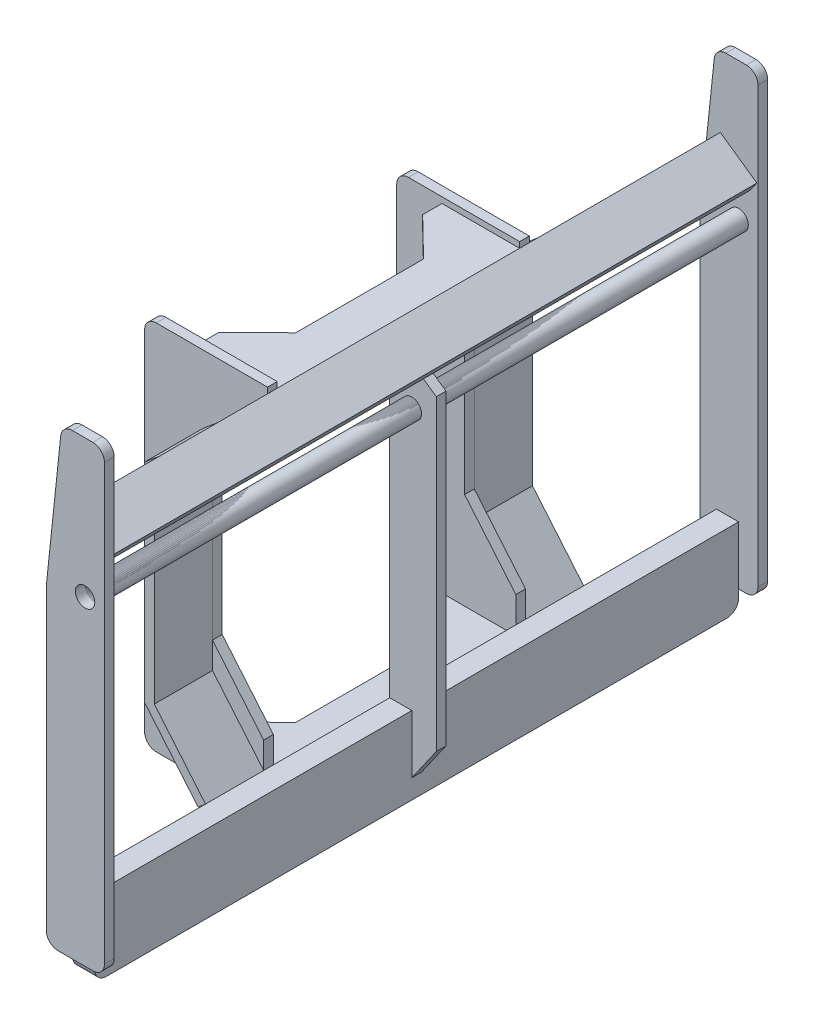
SolidWorks part; units mm, degrees
ref_plane "Front Plane" through (0, 0, 0) normal (0, 0, 1) x (1, 0, 0)
ref_plane "Top Plane" through (0, 0, 0) normal (0, 1, 0) x (1, 0, 0)
ref_plane "Right Plane" through (0, 0, 0) normal (1, 0, 0) x (0, 0, -1)
sketch "Sketch1" plane through (0, 0, 0) normal (0, 0, 1) x (1, 0, 0)
  line L0 (0, 1180) -> (0, 0)
  line L1 (0, 0) -> (-150, 0)
  line L2 (-150, 0) -> (-150, 800)
  line L3 (-150, 800) -> (-110, 1180)
  line L4 (-110, 1180) -> (0, 1180)
  dimension "D1" = 1180
  dimension "D2" = 150
  dimension "D3" = 110
  dimension "D4" = 800
extrude "Boss-Extrude1" add sketch "Sketch1" along normal blind 25 from offset 830
extrude "Boss-Extrude2" add sketch "Sketch1<2>" against normal blind 25 from offset 830 separate body offset against normal yes
sketch "Sketch1<2>" plane through (0, 0, 0) normal (0, 0, 1) x (1, 0, 0) same geometry as "Sketch1"
sketch "Sketch2" plane through (0, 0, -830) normal (0, 0, 1) x (1, 0, 0)
  line L0 (-3, 930) -> (-97.2025, 995.9613)
  line L1 (-3, 930) -> (-20.2073, 905.4254)
  line L2 (-97.2025, 995.9613) -> (-114.4098, 971.3867)
  line L3 (-20.2073, 905.4254) -> (-114.4098, 971.3867)
  line L4 (0, 0) -> (0, 1180) construction
  line L5 (0, 1180) -> (-110, 1180) construction
  line L6 (-150, 0) -> (0, 0) construction
  line L7 (-107, 150) -> (-50, 150)
  line L8 (-107, 150) -> (-107, -50)
  line L9 (-107, -50) -> (-50, -50)
  line L10 (-50, 150) -> (-50, -50)
  line M11 (-150, 0) -> (0, 0)
  dimension "D1" = 30
  dimension "D2" = 115
  dimension "D3" = 3
  dimension "D4" = 250
  dimension "D5" = 55
  dimension "D6" = 57
  dimension "D7" = 50
  dimension "D8" = 150
  dimension "D9" = 200
extrude "Boss-Extrude3" add sketch "Sketch2" along normal up to surface (1660 mm away) contours L3 L1 L0 L2 | L10 L7 L8 M11 | L10 L8 L9 M11 region at (-58.7049, 950.6934, -830) region at (-78.5, 75, -830) region at (-78.5, -25, -830) up to face at (-82, 632, 830)
sketch "Sketch3" plane through (0, 0, 0) normal (0, 0, 1) x (1, 0, 0)
  line L0 (-107, 966.1983) -> (-20.2073, 905.4254)
  line L1 (-20.2073, 905.4254) -> (13, 882.1734)
  line L2 (13, 882.1734) -> (13, 89.9733)
  line L3 (13, 89.9733) -> (-50, 0)
  line L4 (-50, 150) -> (-50, 0) construction
  line L5 (-50, 0) -> (-50, 150)
  line L6 (-50, 150) -> (-107, 150)
  line L7 (-107, 150) -> (-107, 966.1983)
  line L8 (-20.2073, 905.4254) -> (-114.4098, 971.3867) construction
  line L9 (-50, 0) -> (0, 0) construction
  dimension "D1" = 120
  dimension "D2" = 150
  dimension "D3" = 55
extrude "Boss-Extrude4" add sketch "Sketch3" along normal mid plane 25 contours L7 L6 L5 L3 L2 L1 L0 region at (-46.4176, 508.0101, 0)
sketch "Sketch4" plane through (0, 0, 855) normal (0, 0, 1) x (1, 0, 0)
  line L0 (0, 0) -> (0, 1180) construction
  line L1 (0, 1180) -> (-110, 1180) construction
  circle A0 centre (-50, 825) radius 25
  dimension "D1" = 50
  dimension "D2" = 50
  dimension "D3" = 355
extrude "Cut-Extrude1" cut sketch "Sketch4" against normal through all
sketch "Sketch5" plane through (0, 0, 855) normal (0, 0, 1) x (1, 0, 0)
  circle A0 centre (-50, 825) radius 25 construction
  circle A1 centre (-50, 825) radius 25
  circle A2 centre (-50, 825) radius 24.99
  dimension "D1" = 0.01
extrude "Boss-Extrude5" add sketch "Sketch5" against normal up to surface (1710 mm away) up to face at (-25, 825, -855)
sketch "Sketch6" plane through (0, 0, -12.5) normal (0, 0, -1) x (-1, 0, 0)
  line L0 (50, 150) -> (107, 150) construction
  line L1 (114.4098, 971.3867) -> (20.2073, 905.4254) construction
  line L3 (50, 150) -> (107, 150)
  line L4 (114.4098, 971.3867) -> (67.3085, 938.4061)
  line L7 (97.2025, 995.9613) -> (97.2025, 1010.9613)
  line L8 (114.4098, 971.3867) -> (67.3085, 938.4061)
  line L9 (50, 150) -> (107, 150)
  line L10 (97.2025, 1010.9613) -> (414, 1010.9613)
  line L11 (414, 1010.9613) -> (414, 52.9613)
  line L12 (414, 52.9613) -> (107, 52.9613)
  line L13 (107, 0) -> (107, 150) construction
  line L14 (50, 150) -> (239, 375.2414)
  line L15 (239, 375.2414) -> (239, 783.8144)
  line L16 (239, 783.8144) -> (67.3085, 938.4061)
  line L17 (150, 800) -> (150, 0) construction
  line L18 (107, 150) -> (107, 52.9613)
  line L19 (97.2025, 995.9613) -> (114.4098, 971.3867)
  line M2 (107, 150) -> (107, 966.1983)
  dimension "D1" = 77
  dimension "D2" = 175
  dimension "D3" = 89
  dimension "D4" = 50
  dimension "D5" = 15
  dimension "D6" = 958
  dimension "D7" = 57.5
extrude "Boss-Extrude6" add sketch "Sketch6" along normal blind 25 from offset 300 contours L7 L19 L4 L16 L15 L14 L18 L12 L11 L10 M2 region at (-290.6194, 520.2319, -12.5)
sketch "Sketch7" plane through (0, 0, -337.5) normal (0, 0, -1) x (-1, 0, 0)
  line L0 (107, 150) -> (239, 307.3115)
  line L1 (239, 307.3115) -> (239, 823.6719)
  line L2 (239, 823.6719) -> (107, 934.433)
  line L4 (239, 375.2414) -> (239, 783.8144) construction
  line L11 (107, 902.6677) -> (107, 966.1983) construction
  point P6 (0, 0)
  point P7 (107, 934.433)
  point P9 (239, 843.2411)
  point P11 (0, 0)
  dimension "D1" = 130
  dimension "D2" = 140
extrude "Extrude-Thin2" add sketch "Sketch7" along normal blind 150 separate body thin thin type one direction wall 25
sketch "Sketch8" plane through (397.3283, 333.398, 0) normal (0.766, 0.6428, 0) x (0, 0, -1)
  line L4 (337.5, 809.5955) -> (337.5, 784.5955)
  line L5 (337.5, 784.5955) -> (487.5, 784.5955)
  line L6 (487.5, 784.5955) -> (487.5, 809.5955)
  line L7 (487.5, 809.5955) -> (337.5, 809.5955)
  line L8 (337.5, 809.5955) -> (337.5, 784.5955)
  line L9 (337.5, 784.5955) -> (487.5, 784.5955)
  line L10 (487.5, 784.5955) -> (487.5, 809.5955)
  line L11 (487.5, 809.5955) -> (337.5, 809.5955)
  dimension "D1" = 0
extrude "Boss-Extrude8" add sketch "Sketch8" along normal up to next separate body
mirror "Mirror2" about plane through (0, 0, 0) normal (0, 0, 1) of bodies 108 107
ref_plane "Plane1" through (0, 995.9613, 0) normal (0, 1, 0) x (1, 0, 0)
sketch "Sketch9" plane through (0, 995.9613, 0) normal (0, 1, 0) x (1, 0, 0)
  line L0 (-297.2025, 312.5) -> (-97.2025, 312.5)
  line L1 (-97.2025, 312.5) -> (-414, 312.5) construction
  line L2 (-97.2025, -830) -> (-97.2025, 312.5) construction
  line L3 (-97.2025, 312.5) -> (-97.2025, -312.5)
  line L4 (-97.2025, -312.5) -> (-297.2025, -312.5)
  line L5 (-97.2025, -312.5) -> (-414, -312.5) construction
  line L6 (-297.2025, -312.5) -> (-297.2025, -262.5)
  line L7 (-297.2025, -262.5) -> (-197.2025, -164.8664)
  line L8 (-197.2025, -164.8664) -> (-197.2025, 164.8664)
  line L9 (-197.2025, 164.8664) -> (-297.2025, 262.5)
  line L10 (-297.2025, 262.5) -> (-297.2025, 312.5)
  point P6 (-197.2025, 164.8664)
  point P16 (0, 0)
  point P17 (0, 0)
  dimension "D1" = 100
  dimension "D2" = 50
  dimension "D3" = 200
extrude "Boss-Extrude9" add sketch "Sketch9" against normal blind 25
pattern_linear "LPattern1" count 2 spacing 870 along (0, -1, 0) of "Boss-Extrude9"
fillet "Fillet1" radius 30 14 edges at (0, 1180, -842.5) (-110, 1180, -842.5) (0, 1180, 842.5) (-110, 1180, 842.5) (-414, 1010.9613, 325) (-414, 1010.9613, -325) (-150, 0, -842.5) (0, 0, -842.5) (0, 0, 842.5) (-150, 0, 842.5) (-78.5, -50, -830) (-78.5, -50, 830) (-414, 52.9613, 325) (-414, 52.9613, -325)
